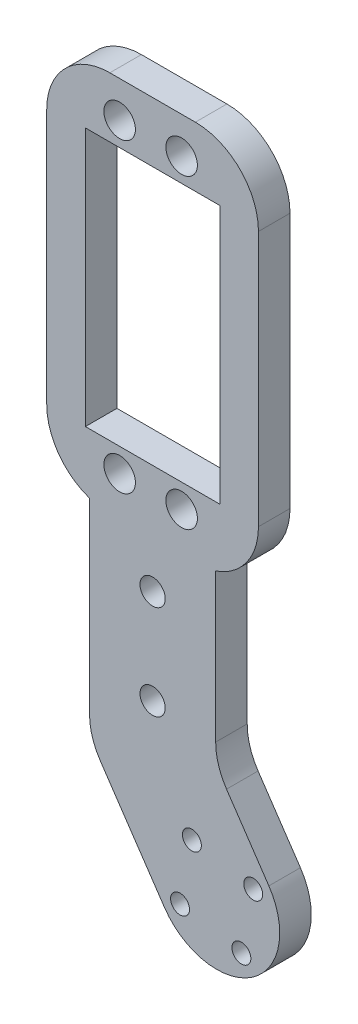
SolidWorks part; units mm, degrees
ref_plane "Front Plane" through (0, 0, 0) normal (0, 0, 1) x (1, 0, 0)
ref_plane "Top Plane" through (0, 0, 0) normal (0, 1, 0) x (1, 0, 0)
ref_plane "Right Plane" through (0, 0, 0) normal (1, 0, 0) x (0, 0, -1)
sketch "Sketch1" plane through (0, 0, 0) normal (0, 0, 1) x (1, 0, 0)
  line L0 (0, 0) -> (-10.15, 0) construction
  line L1 (-10.15, 0) -> (-10.15, 1015) construction
  line L2 (-10.15, 15) -> (0, 0) construction
  line L3 (-0.15, -17.6221) -> (-0.15, 0)
  line L4 (-20.15, 11.9346) -> (-8.2821, -5.6042)
  line L5 (-20.15, 11.9346) -> (-20.15, 104.6203)
  line L6 (-0.15, 18.0654) -> (8.2821, 5.6042)
  line L7 (-18.4321, 9.3958) -> (-8.2821, -5.6042) construction
  line L8 (-0.15, 18.0654) -> (-0.15, 104.6203)
  line L9 (-20.15, 0) -> (-20.15, 1015) construction
  line L10 (-0.15, 0) -> (-0.15, 1015) construction
  line L11 (-20.15, 104.6203) -> (-0.15, 104.6203)
  line L12 (-1.8679, 20.6042) -> (8.2821, 5.6042) construction
  circle A0 centre (0, 0) radius 1.5 construction
  circle A1 centre (0, 0) radius 10
  dimension "D3" = 3
  dimension "D4" = 20
  dimension "D1" = 15
  dimension "D2" = 10.15
  dimension "D5" = 10
  dimension "D6" = 10
extrude "Boss-Extrude1" add sketch "Sketch1" along normal blind 5 contours A1 L6 L8 L11 L5 L4 | A1 region at (-10.0367, 54.6913, 0) region at (0, 0, 0)
sketch "Sketch2" plane through (0, 0, 5) normal (0, 0, 1) x (1, 0, 0)
  line L0 (0, 0) -> (-11.1439, 16.4689) construction
  line L1 (-20.15, 11.9346) -> (-8.2821, -5.6042) construction
  line L2 (8.2821, 5.6042) -> (-8.2821, -5.6042) construction
  line L3 (-10.15, 104.6203) -> (-10.15, 9.6832) construction
  line L4 (-20.15, 104.6203) -> (-0.15, 104.6203) construction
  circle A0 centre (0, 0) radius 1.5 construction
  arc A1 (-8.2821, -5.6042) -> (8.2821, 5.6042) centre (0, 0) ccw construction
  arc A2 (-8.2821, -5.6042) -> (8.2821, 5.6042) centre (0, 0) ccw construction
  circle A3 centre (-3.9229, 5.7975) radius 1.5
  circle A4 centre (5.7975, 3.9229) radius 1.5
  circle A5 centre (3.9229, -5.7975) radius 1.5
  circle A6 centre (-5.7975, -3.9229) radius 1.5
  circle A7 centre (-10.15, 21.7975) radius 2
  circle A8 centre (-10.15, 36.7975) radius 2
  point P21 (0, 0)
  dimension "D1" = 3
  dimension "D2" = 3
  dimension "D5" = 4
  dimension "D7" = 4
  dimension "D3" = 7
  dimension "D6" = 16
  dimension "D8" = 15
  dimension "D4" = 4
sketch "Sketch3" plane through (0, 0, 5) normal (0, 0, 1) x (1, 0, 0)
  line L0 (-10.15, 59.6203) -> (-10.15, 89.6203) construction
  line L1 (-10.15, 104.6203) -> (-10.15, 11.1052) construction
  line L2 (-20.15, 104.6203) -> (-0.15, 104.6203) construction
  line L3 (-10.15, 44.6203) -> (-10.15, 104.6203) construction
  line L4 (0.5, 54.1203) -> (-20.8, 54.1203)
  line L5 (0.5, 54.1203) -> (0.5, 95.1203)
  line L6 (0.5, 95.1203) -> (-20.8, 95.1203)
  line L7 (-20.8, 54.1203) -> (-20.8, 95.1203)
  line L8 (0.5, 54.1203) -> (-20.8, 95.1203) construction
  line L9 (0.5, 95.1203) -> (-20.8, 54.1203) construction
  circle A0 centre (-10.15, 84.7703) radius 1.25 construction
  circle A1 centre (-5.55, 50.3703) radius 2.5
  circle A2 centre (-15.3737, 50.3703) radius 2.5
  circle A3 centre (-15.3737, 98.8703) radius 2.5
  circle A4 centre (-5.55, 98.8703) radius 2.5
  point P9 (-10.15, 74.6203)
  point P23 (-12.153, 80.1436)
  point P25 (-10.15, 74.6203)
  dimension "D1" = 2.5
  dimension "D2" = 3.75
  dimension "D3" = 10.15
  dimension "D4" = 41
  dimension "D5" = 41
  dimension "D6" = 3.75
  dimension "D7" = 21.3
  dimension "D8" = 30
sketch "Sketch4" plane through (0, 0, 5) normal (0, 0, 1) x (1, 0, 0)
  line L0 (0.5, 95.1203) -> (-20.8, 54.1203) construction
  line L1 (6.6293, 44.6203) -> (-26.9293, 44.6203)
  line L2 (6.6293, 44.6203) -> (6.6293, 104.6203)
  line L3 (6.6293, 104.6203) -> (-26.9293, 104.6203)
  line L4 (-26.9293, 44.6203) -> (-26.9293, 104.6203)
  line L5 (6.6293, 44.6203) -> (-26.9293, 104.6203) construction
  line L6 (6.6293, 104.6203) -> (-26.9293, 44.6203) construction
  line L7 (-20.15, 104.6203) -> (-0.15, 104.6203) construction
  point P0 (-10.15, 74.6203)
  dimension "D1" = 60
extrude "Boss-Extrude2" add sketch "Sketch4" against normal blind 5
extrude "Cut-Extrude1" cut sketch "Sketch3" against normal blind 5
fillet "Fillet1" radius 10 4 edges at (-26.9293, 104.6203, 2.5) (6.6293, 104.6203, 2.5) (6.6293, 44.6203, 2.5) (-26.9293, 44.6203, 2.5)
extrude "Cut-Extrude2" cut sketch "Sketch2" against normal blind 5
fillet "Fillet2" radius 10 2 edges at (-0.15, 18.0654, 2.5) (-20.15, 11.9346, 2.5)
